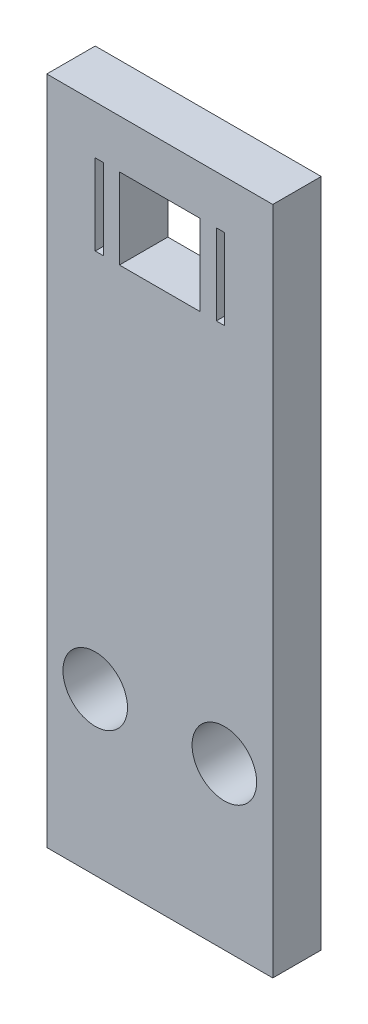
SolidWorks part; units mm, degrees
ref_plane "Front Plane" through (0, 0, 0) normal (0, 0, 1) x (1, 0, 0)
ref_plane "Top Plane" through (0, 0, 0) normal (0, 1, 0) x (1, 0, 0)
ref_plane "Right Plane" through (0, 0, 0) normal (1, 0, 0) x (0, 0, -1)
sketch "Sketch1" plane through (0, 0, 0) normal (0, 0, 1) x (1, 0, 0)
  line L0 (4.5, 38.5) -> (4.5, 33.5)
  line L1 (0, 0) -> (14, 0)
  line L2 (0, 0) -> (0, 41.5)
  line L3 (0, 41.5) -> (14, 41.5)
  line L4 (14, 0) -> (14, 41.5)
  line L9 (3, 38.5) -> (11, 38.5)
  line L10 (3, 38.5) -> (3, 33.5)
  line L11 (3, 33.5) -> (11, 33.5)
  line L12 (11, 38.5) -> (11, 33.5)
  line L13 (3.5, 38.5) -> (10.5, 38.5)
  line L14 (3.5, 38.5) -> (3.5, 33.5)
  line L15 (3.5, 33.5) -> (10.5, 33.5)
  line L16 (10.5, 38.5) -> (10.5, 33.5)
  line L17 (9.5, 38.5) -> (9.5, 33.5)
  circle A0 centre (3, 10) radius 2
  circle A1 centre (11, 10) radius 2
  dimension "D7" = 4
  dimension "D8" = 10
  dimension "D9" = 10
  dimension "D11" = 3
  dimension "D1" = 14
  dimension "D2" = 41.5
  dimension "D3" = 8
  dimension "D4" = 5
  dimension "D5" = 38.5
  dimension "D6" = 3
  dimension "D10" = 3
  dimension "D12" = 7
  dimension "D13" = 0.5
  dimension "D14" = 5
  dimension "D15" = 1
extrude "Boss-Extrude3" add sketch "Sketch1" along normal blind 3 contours L1 L4 L3 L2 A1 A0 L9 L13 L12 L11 L15 L10 | L9 L14 L11 L0 | L13 L17 L15 L16 region at (4, 36, 0) region at (10, 36, 0) region at (7, 20.0913, 0)
